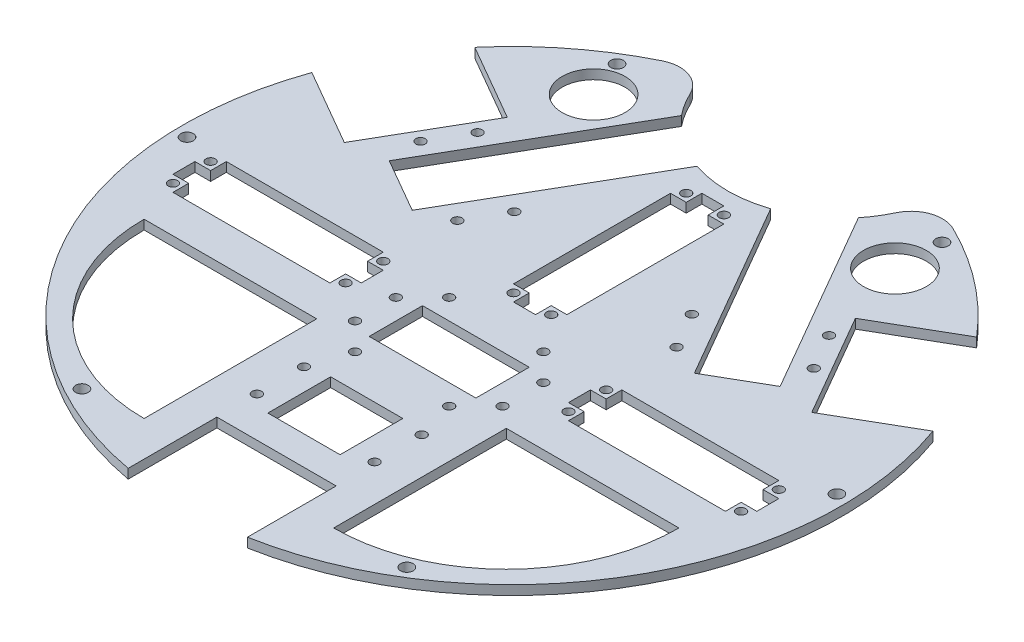
SolidWorks part; units mm, degrees
ref_plane "Alzado" through (0, 0, 0) normal (0, 0, 1) x (1, 0, 0)
ref_plane "Planta" through (0, 0, 0) normal (0, 1, 0) x (1, 0, 0)
ref_plane "Vista lateral" through (0, 0, 0) normal (1, 0, 0) x (0, 0, -1)
sketch "Croquis1" plane through (0, 0, 0) normal (0, 1, 0) x (1, 0, 0)
  circle A0 centre (0, 0) radius 105
  dimension "D1" = 210
extrude "Saliente-Extruir1" add sketch "Croquis1" along normal blind 3
sketch "Croquis2" plane through (0, 3, 0) normal (0, 1, 0) x (1, 0, 0)
  line L0 (-35.7167, 98.7386) -> (35.7167, 98.7386) construction
  line L1 (-29.7198, 68.7386) -> (25.5389, 68.7386) construction
  line L2 (0, 105) -> (0, 68.7386) construction
  arc A0 (35.7167, 98.7386) -> (-35.7167, 98.7386) centre (0, 105) cw
  circle A2 centre (0, 0) radius 105 construction
  arc A3 (-35.7167, 98.7386) -> (35.7167, 98.7386) centre (0, 0) cw
  dimension "D1" = 30
extrude "Cortar-Extruir1" cut sketch "Croquis2" against normal up to surface (3 mm away) up to face at (0, 0, 105)
fillet "Redondeo1" radius 10 2 edges at (35.7167, 1.5, -98.7386) (-35.7167, 1.5, -98.7386)
sketch "Croquis3" plane through (0, 3, 0) normal (0, 1, 0) x (1, 0, 0)
  line L0 (0, 0) -> (0, -105) construction
  line L1 (0, 0) -> (90.9327, 52.5) construction
  line L2 (0, 0) -> (-90.9327, 52.5) construction
  line L4 (-19, -105) -> (19, -105)
  line L5 (-19, -105) -> (-19, -75)
  line L6 (-19, -75) -> (19, -75)
  line L7 (19, -105) -> (19, -75)
  arc A0 (-46.2555, 94.2626) -> (46.2555, 94.2626) centre (0, 0) ccw construction
  dimension "D1" = 120
  dimension "D2" = 120
  dimension "D3" = 38
  dimension "D4" = 30
  dimension "D5" = 19
extrude "Cortar-Extruir2" cut sketch "Croquis3" against normal through all
pattern_circular "MatrizC2" count 3 over 360 about axis through (0, 3, 0) along (0, 1, 0) of "Cortar-Extruir2"
sketch "Croquis4" plane through (0, 3, 0) normal (0, 1, 0) x (1, 0, 0)
  line L0 (-93, -8) -> (-93, 2.464)
  line L1 (-88, -3) -> (-38, -3)
  line L2 (-93, -8) -> (-93, -15)
  line L3 (-88, -20) -> (-38, -20)
  line L4 (-33, -8) -> (-33, -15)
  line L5 (-105, 0) -> (105, 0) construction
  line L6 (-93, 9.464) -> (-93, 8.5)
  line L7 (-105, 15.1341) -> (-105, -14.5482) construction
  line L8 (-93, -8) -> (-88, -8)
  line L9 (-88, -3) -> (-88, -8)
  line L10 (0, 95.3331) -> (0, -118.7147) construction
  line L11 (-33, -15) -> (-38, -15)
  line L12 (-93, -15) -> (-88, -15)
  line L13 (-88, -20) -> (-88, -15)
  line L14 (-38, -20) -> (-38, -15)
  line L15 (33, -15) -> (38, -15)
  line L16 (-33, -8) -> (-38, -8)
  line L17 (-38, -3) -> (-38, -8)
  line L18 (33, -8) -> (33, -15)
  line L19 (33, -8) -> (38, -8)
  line L20 (38, -3) -> (38, -8)
  line L21 (38, -20) -> (38, -15)
  line L22 (93, -8) -> (88, -8)
  line L23 (93, -15) -> (88, -15)
  line L24 (93, -8) -> (93, -15)
  line L25 (88, -20) -> (38, -20)
  line L26 (88, -3) -> (38, -3)
  line L27 (88, -3) -> (88, -8)
  line L28 (88, -20) -> (88, -15)
  arc A1 (-98.9315, 35.1788) -> (-19, -103.2666) centre (0, 0) ccw construction
  arc A2 (19, -103.2666) -> (98.9315, 35.1788) centre (0, 0) ccw construction
  dimension "D2" = 17
  dimension "D3" = 20
  dimension "D4" = 12
  dimension "D5" = 5
  dimension "D6" = 60
  dimension "D7" = 5
  dimension "D8" = 5
  dimension "D9" = 5
  dimension "D10" = 5
  dimension "D11" = 50
  dimension "D12" = 7
  dimension "D13" = 50
extrude "Cortar-Extruir3" cut sketch "Croquis4" against normal through all contours L17 L1 L9 L8 L0 L2 L12 L13 L3 L14 L11 L4 L16 | L25 L28 L23 L24 L22 L27 L26 L20 L19 L18 L15 L21 region at (-63, 3, 11.5) region at (63, 3, 11.5)
sketch "Croquis5" plane through (0, 3, 0) normal (0, 1, 0) x (1, 0, 0)
  line L0 (-93, -8) -> (-88, -8) construction
  line L1 (-88, -3) -> (-88, -8) construction
  line L2 (0, -118.3308) -> (0, 105) construction
  circle A0 centre (-90.5, -5.5) radius 1.5
  circle A1 centre (90.5, -5.5) radius 1.5
  dimension "D1" = 3
  dimension "D2" = 2.5
  dimension "D3" = 2.5
extrude "Cortar-Extruir4" cut sketch "Croquis5" against normal through all
sketch "Croquis6" plane through (0, 3, 0) normal (0, 1, 0) x (1, 0, 0)
  line L0 (-93, -15) -> (-88, -15) construction
  line L1 (-88, -20) -> (-88, -15) construction
  line L2 (0, -112.2563) -> (0, 102.9109) construction
  circle A0 centre (-90.5, -17.5) radius 1.5
  circle A1 centre (90.5, -17.5) radius 1.5
  point P2 (-90.5, -15)
  dimension "D1" = 3
  dimension "D2" = 2.5
  dimension "D3" = 2.5
extrude "Cortar-Extruir5" cut sketch "Croquis6" against normal through all
sketch "Croquis7" plane through (0, 3, 0) normal (0, 1, 0) x (1, 0, 0)
  line L0 (-33, -15) -> (-38, -15) construction
  line L1 (-38, -20) -> (-38, -15) construction
  line L2 (0, -114.5727) -> (0, 110.2304) construction
  circle A0 centre (-35.5, -17.5) radius 1.5
  circle A1 centre (35.5, -17.5) radius 1.5
  dimension "D1" = 3
  dimension "D2" = 2.5
  dimension "D3" = 2.5
extrude "Cortar-Extruir6" cut sketch "Croquis7" against normal through all
sketch "Croquis8" plane through (0, 3, 0) normal (0, 1, 0) x (1, 0, 0)
  line L0 (-38, -3) -> (-38, -8) construction
  line L1 (-33, -8) -> (-38, -8) construction
  line L2 (0, -113.2251) -> (0, 105.5481) construction
  circle A0 centre (-35.5, -5.5) radius 1.5
  circle A1 centre (35.5, -5.5) radius 1.5
  dimension "D1" = 3
  dimension "D3" = 2.5
  dimension "D2" = 2.5
extrude "Cortar-Extruir8" cut sketch "Croquis8" against normal blind 10
sketch "Croquis10" plane through (0, 3, 0) normal (0, 1, 0) x (1, 0, 0)
  line L0 (0, 68.7386) -> (0, -75) construction
  line L1 (19, -75) -> (-19, -75) construction
  line L2 (0, -75) -> (-19, -75) construction
  line L4 (-3.5, 64) -> (3.5, 64)
  line L5 (-8.5, 59) -> (-8.5, 9)
  line L6 (-3.5, 4) -> (3.5, 4)
  line L7 (8.5, 59) -> (8.5, 9)
  line L10 (8.5, 9) -> (3.5, 9)
  line L11 (3.5, 4) -> (3.5, 9)
  line L14 (-8.5, 9) -> (-3.5, 9)
  line L15 (-3.5, 4) -> (-3.5, 9)
  line L18 (-8.5, 59) -> (-3.5, 59)
  line L19 (-3.5, 64) -> (-3.5, 59)
  line L22 (8.5, 59) -> (3.5, 59)
  line L23 (3.5, 64) -> (3.5, 59)
  arc A0 (-32.8037, 89.5468) -> (32.8037, 89.5468) centre (0, 105) ccw construction
  dimension "D2" = 8.5
  dimension "D3" = 8.5
  dimension "D4" = 4
  dimension "D5" = 5
  dimension "D6" = 5
  dimension "D7" = 5
  dimension "D8" = 5
  dimension "D9" = 5
  dimension "D10" = 5
  dimension "D11" = 5
  dimension "D12" = 7
  dimension "D13" = 50
extrude "Cortar-Extruir9" cut sketch "Croquis10" against normal through all
sketch "Croquis11" plane through (0, 3, 0) normal (0, 1, 0) x (1, 0, 0)
  line L0 (-3.5, 64) -> (-3.5, 59) construction
  line L1 (-3.5, 59) -> (-8.5, 59) construction
  line L2 (8.5, 59) -> (3.5, 59) construction
  line L3 (3.5, 59) -> (3.5, 64) construction
  circle A0 centre (-6, 61.5) radius 1.5
  circle A1 centre (6, 61.5) radius 1.5
  dimension "D1" = 3
  dimension "D2" = 3
  dimension "D3" = 2.5
  dimension "D4" = 2.5
  dimension "D5" = 2.5
  dimension "D6" = 2.5
extrude "Cortar-Extruir10" cut sketch "Croquis11" against normal through all
sketch "Croquis12" plane through (0, 3, 0) normal (0, 1, 0) x (1, 0, 0)
  line L0 (-8.5, 9) -> (-3.5, 9) construction
  line L1 (-3.5, 9) -> (-3.5, 4) construction
  line L2 (3.5, 9) -> (8.5, 9) construction
  line L3 (3.5, 4) -> (3.5, 9) construction
  circle A0 centre (-6, 6.5) radius 1.5
  circle A1 centre (6, 6.5) radius 1.5
  point P6 (-3.5, 6.5)
  dimension "D1" = 3
  dimension "D2" = 3
  dimension "D3" = 2.5
  dimension "D4" = 2.5
  dimension "D5" = 2.5
  dimension "D6" = 2.5
extrude "Cortar-Extruir11" cut sketch "Croquis12" against normal through all
sketch "Croquis14" plane through (0, 3, 0) normal (0, 1, 0) x (1, 0, 0)
  line L0 (-19, -103.2666) -> (-19, -47.2666) construction
  circle A0 centre (-19, -47.2666) radius 1.5
  circle A1 centre (-19, -62.2666) radius 1.5
  circle A2 centre (18.5, -47.2666) radius 1.5
  circle A3 centre (18.5, -62.2666) radius 1.5
  dimension "D2" = 3
  dimension "D3" = 3
  dimension "D4" = 15
  dimension "D5" = 3
  dimension "D6" = 37.5
  dimension "D7" = 56
  dimension "D8" = 3
  dimension "D9" = 37.5
  dimension "D10" = 15
  dimension "D1" = 56
extrude "Cortar-Extruir15" cut sketch "Croquis14" against normal through all
sketch "Croquis16" plane through (0, 3, 0) normal (0, 1, 0) x (1, 0, 0)
  line L0 (-85.1993, -32) -> (-30.1993, -32)
  line L1 (-30.1993, -32) -> (-30.1993, -87)
  line L2 (-88, -20) -> (-38, -20) construction
  line L3 (0, -120.8087) -> (0, 122.8714) construction
  line L4 (30.1993, -32) -> (30.1993, -87)
  line L5 (85.1993, -32) -> (30.1993, -32)
  arc A2 (-85.1993, -32) -> (-30.1993, -87) centre (-30.1993, -32) ccw
  arc A3 (-98.9315, 35.1788) -> (-19, -103.2666) centre (0, 0) ccw construction
  arc A4 (85.1993, -32) -> (30.1993, -87) centre (30.1993, -32) cw
  point P3 (-63, -20)
  dimension "D2" = 44
  dimension "D1" = 55
  dimension "D3" = 12
extrude "Cortar-Extruir18" cut sketch "Croquis16" against normal through all
sketch "Croquis17" plane through (0, 3, 0) normal (0, 1, 0) x (1, 0, 0)
  line L0 (0, 124.2395) -> (0, -136.388) construction
  circle A0 centre (-48, 74) radius 10
  arc A1 (-46.2555, 94.2626) -> (-79.9315, 68.0878) centre (0, 0) ccw construction
  circle A2 centre (48, 74) radius 10
  dimension "D1" = 20
  dimension "D2" = 74
  dimension "D3" = 48
extrude "Cortar-Extruir19" cut sketch "Croquis17" against normal through all
sketch "Croquis19" plane through (0, 3, 0) normal (0, 1, 0) x (1, 0, 0)
  line L0 (-137.1185, -5) -> (163.4508, -5) construction
  line L1 (-27, -1.5) -> (27, -1.5) construction
  line L2 (27, -1.5) -> (27, -38.5) construction
  line L3 (27, -38.5) -> (-27, -38.5) construction
  line L4 (-27, -38.5) -> (-27, -1.5) construction
  line L5 (-20, -1.5) -> (-20, -8.5) construction
  line L6 (-20, -8.5) -> (-27, -8.5) construction
  line L7 (-27, -31.5) -> (-20, -31.5) construction
  line L8 (0, -126.3006) -> (0, 103.8039) construction
  line L9 (-20, -31.5) -> (-20, -38.5) construction
  line L10 (27, -31.5) -> (20, -31.5) construction
  line L11 (20, -31.5) -> (20, -38.5) construction
  line L12 (20, -1.5) -> (20, -8.5) construction
  line L13 (20, -8.5) -> (27, -8.5) construction
  arc A0 (-32.8037, 89.5468) -> (32.8037, 89.5468) centre (0, 105) ccw construction
  circle A1 centre (-15, -35) radius 1.5
  circle A2 centre (15, -35) radius 1.5
  circle A3 centre (23.5, -13.5) radius 1.5
  circle A4 centre (23.5, -26.5) radius 1.5
  circle A5 centre (-23.5, -26.5) radius 1.5
  circle A6 centre (-23.5, -13.5) radius 1.5
  circle A7 centre (-15, -5) radius 1.5
  circle A8 centre (15, -5) radius 1.5
  dimension "D4" = 3.5
  dimension "D5" = 33.5
  dimension "D6" = 7
  dimension "D7" = 7
  dimension "D8" = 7
  dimension "D9" = 7
  dimension "D12" = 7
  dimension "D14" = 5
  dimension "D16" = 3
  dimension "D17" = 5
  dimension "D18" = 3.5
  dimension "D19" = 3
  dimension "D20" = 5
  dimension "D21" = 3.5
  dimension "D13" = 3
  dimension "D15" = 3.5
  dimension "D22" = 3
  dimension "D23" = 3.5
  dimension "D24" = 5
  dimension "D25" = 5
  dimension "D26" = 3.5
  dimension "D27" = 3
  dimension "D28" = 3
  dimension "D29" = 3.5
  dimension "D30" = 5
  dimension "D31" = 3
  dimension "D32" = 3
  dimension "D33" = 5
  dimension "D34" = 3.5
  dimension "D35" = 3.5
  dimension "D36" = 5
  dimension "D1" = 110
  dimension "D2" = 27
  dimension "D3" = 27
  dimension "D10" = 7
  dimension "D11" = 7
  dimension "D37" = 7
  dimension "D38" = 90
extrude "Cortar-Extruir20" cut sketch "Croquis19" against normal through all
sketch "Croquis20" plane through (0, 3, 0) normal (0, 1, 0) x (1, 0, 0)
  line L0 (-19, -47.2666) -> (-12, -47.2666) construction
  line L1 (-12, -47.2666) -> (-12, -45.7666) construction
  line L2 (-12, -45.7666) -> (11, -45.7666)
  line L3 (-12, -45.7666) -> (-12, -65.7666)
  line L4 (-12, -65.7666) -> (11, -65.7666)
  line L5 (11, -45.7666) -> (11, -65.7666)
  circle A0 centre (-19, -47.2666) radius 1.5 construction
  point P20 (0, 0)
  dimension "D1" = 1.5
  dimension "D2" = 20
  dimension "D3" = 23
  dimension "D4" = 7
extrude "Cortar-Extruir21" cut sketch "Croquis20" against normal through all
sketch "Croquis21" plane through (0, 3, 0) normal (0, 1, 0) x (1, 0, 0)
  line L0 (-75.834, 22.6517) -> (-53.684, 61.0167)
  line L1 (-75.834, 22.6517) -> (-38.5949, 1.1517)
  line L2 (-53.684, 61.0167) -> (-16.4449, 39.5167)
  line L3 (-38.5949, 1.1517) -> (-16.4449, 39.5167)
  line L4 (-75.834, 22.6517) -> (-70.334, 32.178)
  line L5 (-75.834, 22.6517) -> (-67.1737, 17.6517)
  line L6 (-70.334, 32.178) -> (-61.6737, 27.178)
  line L7 (-67.1737, 17.6517) -> (-61.6737, 27.178)
  line L8 (-38.5949, 1.1517) -> (-33.0949, 10.678)
  line L9 (-38.5949, 1.1517) -> (-47.2551, 6.1517)
  line L10 (-33.0949, 10.678) -> (-41.7551, 15.678)
  line L11 (-47.2551, 6.1517) -> (-41.7551, 15.678)
  line L12 (-74.4519, 21.0455) -> (-55.4519, 53.9545) construction
  line L13 (-79.9315, 68.0878) -> (-8.5, 26.8468) construction
  line L14 (-8.5, 59) -> (-8.5, 9) construction
  line L15 (0, -111.448) -> (0, 107.1524) construction
  line L20 (-47.2551, 6.1517) -> (-67.1737, 17.6517)
  circle A0 centre (-62.6378, 33.5081) radius 1.5
  circle A1 centre (-55.9878, 45.0263) radius 1.5
  circle A2 centre (-28.275, 29.0263) radius 1.5
  circle A3 centre (-34.925, 17.5081) radius 1.5
  circle A7 centre (28.275, 29.0263) radius 1.5
  circle A8 centre (34.925, 17.5081) radius 1.5
  circle A11 centre (62.6378, 33.5081) radius 1.5
  circle A12 centre (55.9878, 45.0263) radius 1.5
  dimension "D10" = 6
  dimension "D12" = 3
  dimension "D13" = 15
  dimension "D14" = 6
  dimension "D15" = 3
  dimension "D16" = 3
  dimension "D17" = 15
  dimension "D18" = 5
  dimension "D19" = 3
  dimension "D20" = 5
  dimension "D21" = 5
  dimension "D1" = 44.3
  dimension "D2" = 43
  dimension "D3" = 10
  dimension "D4" = 11
  dimension "D5" = 10
  dimension "D6" = 11
  dimension "D7" = 2
  dimension "D8" = 90
  dimension "D9" = 7
  dimension "D11" = 5
extrude "Cortar-Extruir23" cut sketch "Croquis21" against normal blind 10 contours A3 | A2 | A1 | A0 | A7 | A8 | A11 | A12 region at (-62.6378, 3, -33.5081) region at (-55.9878, 3, -45.0263) region at (-28.275, 3, -29.0263) region at (-34.925, 3, -17.5081) region at (28.275, 3, -29.0263) region at (34.925, 3, -17.5081)
sketch "Croquis22" plane through (0, 3, 0) normal (0, 1, 0) x (1, 0, 0)
  circle A0 centre (-100.9681, -2.54) radius 2
  circle A1 centre (-52.6837, 86.1709) radius 2
  circle A2 centre (48.2843, 88.7109) radius 2
  circle A3 centre (100.9681, 2.54) radius 2
  circle A4 centre (52.6837, -86.1709) radius 2
  circle A5 centre (-48.2843, -88.7109) radius 2
  arc A7 (-98.9315, 35.1788) -> (-19, -103.2666) centre (0, 0) ccw construction
  point P18 (0, 0)
  point P19 (0, 0)
  point P21 (2.2149, -1.2436)
  dimension "D1" = 4
  dimension "D2" = 101
  dimension "D3" = 37.7189
  dimension "D4" = 6
extrude "Cortar-Extruir24" cut sketch "Croquis22" against normal through all
sketch "Croquis23" plane through (0, 3, 0) normal (0, 1, 0) x (1, 0, 0)
  line L0 (-62.2583, 23.1654) -> (-27.7583, 82.9212)
  line L1 (-62.2583, 23.1654) -> (-44.9378, 13.1654)
  line L2 (-27.7583, 82.9212) -> (-10.4378, 72.9212)
  line L3 (-44.9378, 13.1654) -> (-10.4378, 72.9212)
  line L4 (-74.4519, 21.0455) -> (-55.4519, 53.9545) construction
  line L7 (0, 105) -> (0, -112.7081) construction
  line L8 (27.7583, 82.9212) -> (10.4378, 72.9212)
  line L9 (62.2583, 23.1654) -> (44.9378, 13.1654)
  line L10 (62.2583, 23.1654) -> (27.7583, 82.9212)
  line L11 (44.9378, 13.1654) -> (10.4378, 72.9212)
  arc A0 (19, -103.2666) -> (98.9315, 35.1788) centre (0, 0) ccw construction
  arc A1 (-32.8037, 89.5468) -> (32.8037, 89.5468) centre (0, 105) ccw construction
  dimension "D1" = 0
  dimension "D2" = 20
  dimension "D3" = 45.5
  dimension "D4" = 69
  dimension "D5" = 33
extrude "Cortar-Extruir25" cut sketch "Croquis23" against normal through all
sketch "Croquis24" plane through (0, 3, 0) normal (0, 1, 0) x (1, 0, 0)
  line L1 (-17, -11.5) -> (17, -11.5)
  line L2 (-17, -11.5) -> (-17, -28.5)
  line L3 (-17, -28.5) -> (17, -28.5)
  line L4 (17, -11.5) -> (17, -28.5)
  circle A0 centre (-23.5, -13.5) radius 1.5 construction
  dimension "D1" = 6.5
  dimension "D2" = 2
  dimension "D3" = 17
  dimension "D4" = 34
extrude "Cortar-Extruir26" cut sketch "Croquis24" against normal through all
